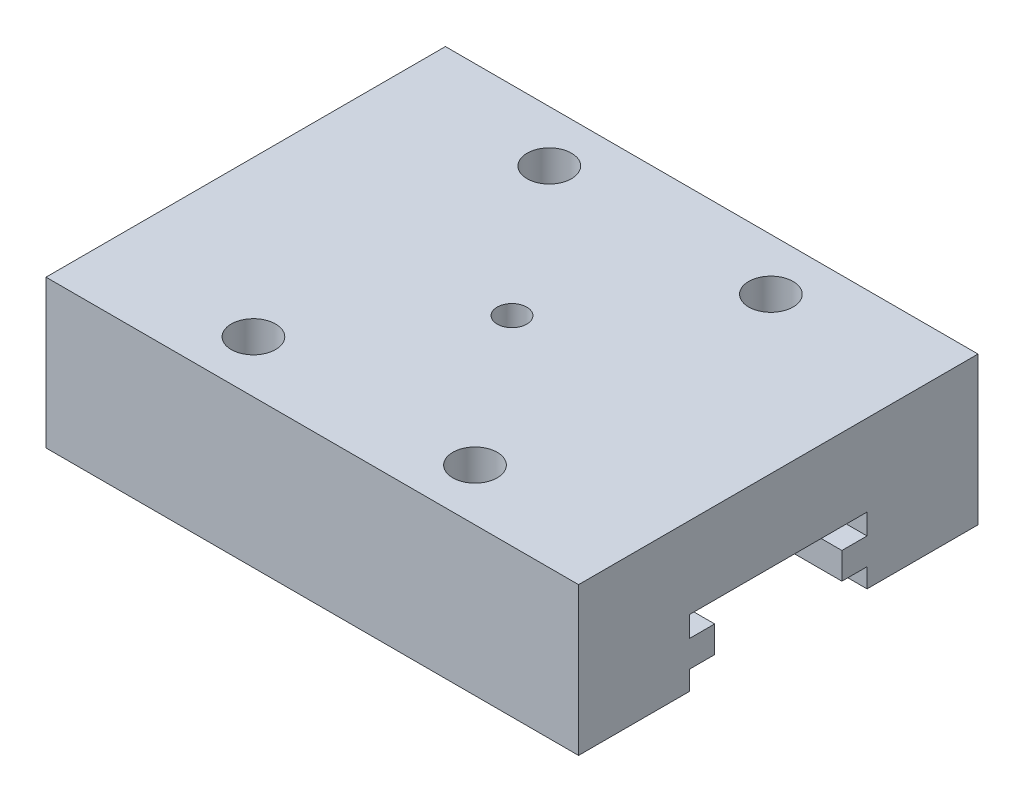
SolidWorks part; units mm, degrees
ref_plane "Alzado" through (0, 0, 0) normal (0, 0, 1) x (1, 0, 0)
ref_plane "Planta" through (0, 0, 0) normal (0, 1, 0) x (1, 0, 0)
ref_plane "Vista lateral" through (0, 0, 0) normal (1, 0, 0) x (0, 0, -1)
sketch "Croquis1" plane through (0, 0, 0) normal (0, 1, 0) x (1, 0, 0)
  line L2 (0, 0) -> (36, 0)
  line L3 (0, 0) -> (0, 27)
  line L4 (0, 27) -> (36, 27)
  line L5 (36, 0) -> (36, 27)
  dimension "D1" = 36
  dimension "D2" = 27
extrude "Saliente-Extruir1" add sketch "Croquis1" along normal blind 10
sketch "Croquis2" plane through (0, 10, 0) normal (0, 1, 0) x (1, 0, 0)
  line L0 (0, 0) -> (36, 0) construction
  line L1 (10.5, 3.5201) -> (25.5, 23.5) construction
  line L2 (18, 0) -> (18, 27) construction
  line L3 (36, 27) -> (0, 27) construction
  circle A0 centre (10.5, 23.5201) radius 1.5
  circle A1 centre (25.5, 23.5) radius 1.5
  circle A2 centre (10.5, 3.5201) radius 1.5
  circle A3 centre (25.5, 3.5) radius 1.5
  circle A4 centre (18, 13.5) radius 1
  point P14 (18, 13.5101)
  dimension "D1" = 3
  dimension "D2" = 15
  dimension "D3" = 15
  dimension "D4" = 20
  dimension "D5" = 20
  dimension "D6" = 3.5
  dimension "D7" = 7.5
  dimension "D8" = 15
  dimension "D9" = 7.5
extrude "Cortar-Extruir1" cut sketch "Croquis2" against normal blind 5
sketch "Croquis3" plane through (36, 0, 0) normal (1, 0, 0) x (0, 0, -1)
  line L0 (0, 0) -> (27, 0) construction
  line L1 (7.5, 0) -> (19.5, 0)
  line L2 (7.5, 0) -> (7.5, 1.3)
  line L3 (7.5, 4.5) -> (19.5, 4.5)
  line L4 (19.5, 0) -> (19.5, 1.3)
  line L5 (13.5, 10) -> (13.5, 0) construction
  line L6 (0, 10) -> (27, 10) construction
  line L7 (7.5, 3.1) -> (7.5, 4.5)
  line L8 (7.5, 3.1) -> (9.2, 3.1)
  line L10 (7.5, 1.3) -> (9.2, 1.3)
  line L11 (9.2, 3.1) -> (9.2, 1.3)
  line L12 (19.5, 1.3) -> (17.8, 1.3)
  line L13 (19.5, 3.1) -> (17.8, 3.1)
  line L14 (17.8, 3.1) -> (17.8, 1.3)
  line L15 (19.5, 3.1) -> (19.5, 4.5)
  dimension "D2" = 4.5
  dimension "D3" = 6
  dimension "D4" = 1.8
  dimension "D5" = 1.7
  dimension "D6" = 1.4
extrude "Cortar-Extruir2" cut sketch "Croquis3" against normal up to surface (36 mm away) up to face at (0, 5, -13.5)
